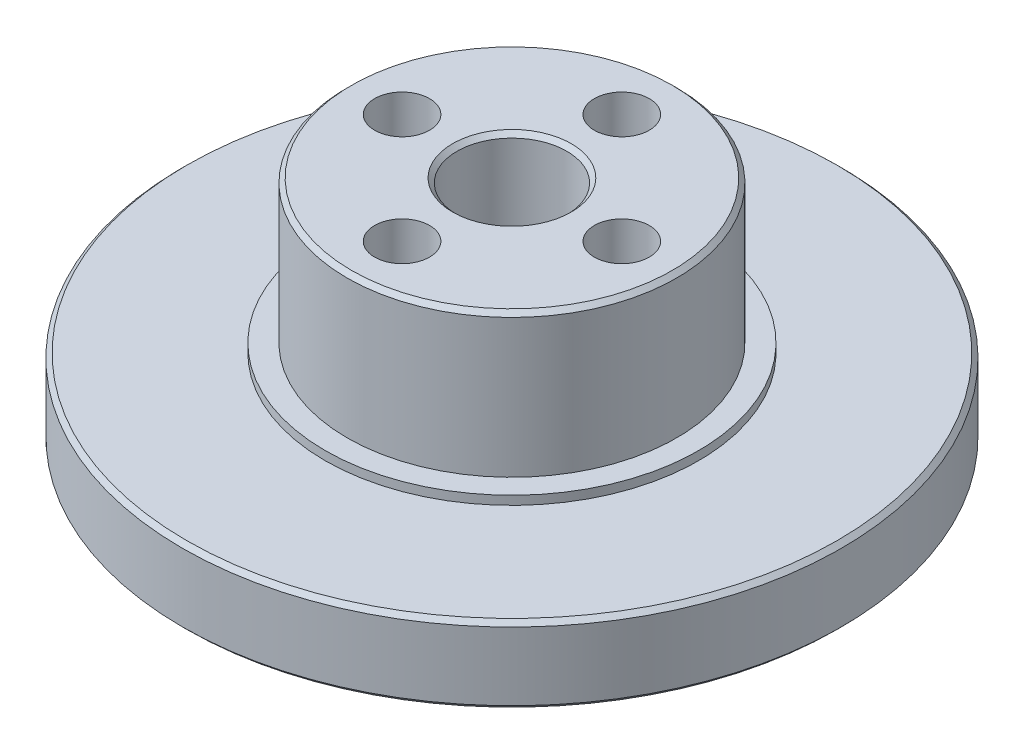
SolidWorks part; units mm, degrees
ref_plane "前视基准面" through (0, 0, 0) normal (0, 0, 1) x (1, 0, 0)
ref_plane "上视基准面" through (0, 0, 0) normal (0, 1, 0) x (1, 0, 0)
ref_plane "右视基准面" through (0, 0, 0) normal (1, 0, 0) x (0, 0, -1)
other "Configuration Table"
sketch "草图1" plane through (0, 0, 0) normal (0, 1, 0) x (1, 0, 0)
  circle A0 centre (0, 0) radius 11.525 construction
  circle A1 centre (0, 11.525) radius 1.83
  circle A2 centre (9.9809, 5.7625) radius 1.83
  circle A3 centre (9.9809, -5.7625) radius 1.83
  circle A4 centre (0, -11.525) radius 1.83
  circle A5 centre (-9.9809, -5.7625) radius 1.83
  circle A6 centre (-9.9809, 5.7625) radius 1.83
  circle A8 centre (0, 0) radius 15
  point P18 (0, 0)
  dimension "D1" = 23.05
  dimension "D2" = 3.66
  dimension "D5" = 30
  dimension "D3" = 6
extrude "凸台-拉伸1" add sketch "草图1" along normal blind 2
sketch "草图2" plane through (0, 2, 0) normal (0, 1, 0) x (1, 0, 0)
  circle A0 centre (0, 0) radius 15
extrude "凸台-拉伸2" add sketch "草图2" along normal blind 1.5
sketch "草图3" plane through (0, 3.5, 0) normal (0, 1, 0) x (1, 0, 0)
  circle A0 centre (0, 0) radius 8.5
  dimension "D1" = 17
extrude "凸台-拉伸3" add sketch "草图3" along normal blind 0.4
sketch "草图4" plane through (0, 3.9, 0) normal (0, 1, 0) x (1, 0, 0)
  circle A0 centre (0, 0) radius 7.5
  dimension "D1" = 15
extrude "凸台-拉伸4" add sketch "草图4" along normal blind 6.5
sketch "草图5" plane through (0, 10.4, 0) normal (0, 1, 0) x (1, 0, 0)
  circle A0 centre (0, 5) radius 1.25
  circle A1 centre (5, 0) radius 1.25
  circle A2 centre (0, -5) radius 1.25
  circle A3 centre (-5, 0) radius 1.25
  circle A4 centre (0, 0) radius 2.5
  point P12 (0, 0)
  dimension "D1" = 2.5
  dimension "D2" = 5
  dimension "D4" = 5
  dimension "D3" = 4
extrude "切除-拉伸1" cut sketch "草图5" against normal blind 5
chamfer "倒角1" distance 0.2 angle 45 10 edges at (-9.9809, 0, -3.9325) (-9.9809, 0, 7.5925) (0, 0, 13.355) (9.9809, 0, 7.5925) (9.9809, 0, -3.9325) (0, 0, -9.695) (0, 0, 15) (0, 10.4, 7.5) (0, 3.5, 15) (0, 10.4, 2.5)
sketch "草图7" plane through (0, 5.4, 0) normal (0, 1, 0) x (1, 0, 0)
  circle A2 centre (0, 0) radius 2.5 construction
  circle A3 centre (0, 0) radius 2.5
extrude "切除-拉伸4" cut sketch "草图7" against normal through all
sketch "草图8" plane through (0, 0, 0) normal (0, -1, 0) x (-1, 0, 0)
  circle A0 centre (0, 0) radius 6
  dimension "D1" = 6
extrude "切除-拉伸5" cut sketch "草图8" against normal blind 2
chamfer "倒角2" distance 0.5 angle 45 3 edges at (0, 0, -6) (0, 2, -2.5) (0, 2, -6)
